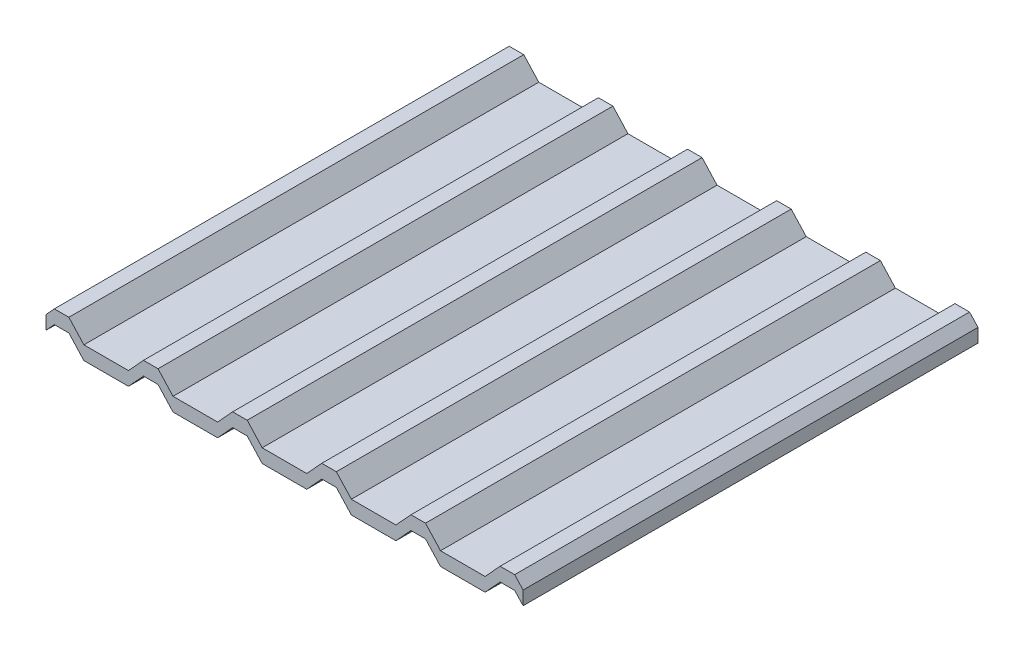
SolidWorks part; units mm, degrees
material "Epoxy, Unfilled"
ref_plane "Plano frontal" through (0, 0, 0) normal (0, 0, 1) x (1, 0, 0)
ref_plane "Plano superior" through (0, 0, 0) normal (0, 1, 0) x (1, 0, 0)
ref_plane "Plano direito" through (0, 0, 0) normal (1, 0, 0) x (0, 0, -1)
sketch "Esboço1" plane through (0, 0, 0) normal (0, 0, 1) x (1, 0, 0)
  line L0 (0, 0) -> (32, 0)
  line L1 (65, -36) -> (163, -36)
  line L3 (0, 0) -> (-33, -36)
  line L4 (32, 0) -> (65, -36)
  line L5 (196, 0) -> (228, 0)
  line L6 (261, -36) -> (359, -36)
  line L7 (196, 0) -> (163, -36)
  line L8 (228, 0) -> (261, -36)
  line L9 (-33, -36) -> (-131, -36)
  line L10 (392, 0) -> (424, 0)
  line L11 (457, -36) -> (555, -36)
  line L12 (392, 0) -> (359, -36)
  line L13 (424, 0) -> (457, -36)
  line L14 (588, 0) -> (620, 0)
  line L15 (653, -36) -> (751, -36)
  line L16 (588, 0) -> (555, -36)
  line L17 (620, 0) -> (653, -36)
  line L18 (-196, 0) -> (-164, 0)
  line L19 (-196, 0) -> (-214.2729, -20)
  line L20 (-164, 0) -> (-131, -36)
  line L23 (784, 0) -> (816, 0)
  line L24 (784, 0) -> (751, -36)
  line L25 (816, 0) -> (834.5668, -20)
  line L26 (784, 30) -> (751, -6)
  line L27 (228, 30) -> (261, -6)
  line L28 (653, -6) -> (751, -6)
  line L29 (0, 30) -> (-33, -6)
  line L30 (424, 30) -> (457, -6)
  line L31 (588, 30) -> (555, -6)
  line L32 (-196, 30) -> (-214.2729, 10)
  line L33 (261, -6) -> (359, -6)
  line L34 (784, 30) -> (816, 30)
  line L35 (0, 30) -> (32, 30)
  line L36 (65, -6) -> (163, -6)
  line L37 (392, 30) -> (359, -6)
  line L38 (588, 30) -> (620, 30)
  line L39 (816, 30) -> (834.5668, 10)
  line L40 (-33, -6) -> (-131, -6)
  line L41 (-196, 30) -> (-164, 30)
  line L42 (-164, 30) -> (-131, -6)
  line L43 (196, 30) -> (228, 30)
  line L44 (32, 30) -> (65, -6)
  line L45 (196, 30) -> (163, -6)
  line L46 (620, 30) -> (653, -6)
  line L47 (392, 30) -> (424, 30)
  line L48 (457, -6) -> (555, -6)
  line L49 (-214.2729, 10) -> (-214.2729, -20)
  line L50 (834.5668, 10) -> (834.5668, -20)
  point P8 (16, -36)
  point P12 (212, -36)
  point P18 (408, -36)
  point P23 (604, -36)
  point P36 (16, -6)
  point P40 (212, -6)
  point P46 (408, -6)
  point P51 (604, -6)
  dimension "D1" = 98
  dimension "D2" = 98
sketch "Esboço2" plane through (0, 0, 0) normal (0, 0, 1) x (1, 0, 0)
  line L0 (0, 30) -> (32, 30)
  line L1 (65, -6) -> (163, -6)
  line L3 (0, 30) -> (-33, -6)
  line L4 (32, 30) -> (65, -6)
  line L5 (196, 30) -> (228, 30)
  line L6 (261, -6) -> (359, -6)
  line L7 (196, 30) -> (163, -6)
  line L8 (228, 30) -> (261, -6)
  line L9 (-33, -6) -> (-131, -6)
  line L10 (392, 30) -> (424, 30)
  line L11 (457, -6) -> (555, -6)
  line L12 (392, 30) -> (359, -6)
  line L13 (424, 30) -> (457, -6)
  line L14 (588, 30) -> (620, 30)
  line L15 (653, -6) -> (751, -6)
  line L16 (588, 30) -> (555, -6)
  line L17 (620, 30) -> (653, -6)
  line L18 (-196, 30) -> (-164, 30)
  line L19 (-196, 30) -> (-214.2729, 10)
  line L20 (-164, 30) -> (-131, -6)
  line L23 (784, 30) -> (816, 30)
  line L24 (784, 30) -> (751, -6)
  line L25 (816, 30) -> (834.5668, 10)
  point P8 (16, -6)
  point P12 (212, -6)
  point P18 (408, -6)
  point P23 (604, -6)
  dimension "D1" = 98
  dimension "D2" = 98
extrude "Ressalto-extrusão1" add sketch "Esboço1" along normal blind 1000 contours L40 L42 L41 L32 L49 L19 L18 L20 L9 L3 L0 L4 L1 L7 L5 L8 L6 L12 L10 L13 L11 L16 L14 L17 L15 L24 L23 L25 L50 L39 L34 L26 L28 L46 L38 L31 L48 L30 L47 L37 L33 L27 L43 L45 L36 L44 L35 L29
